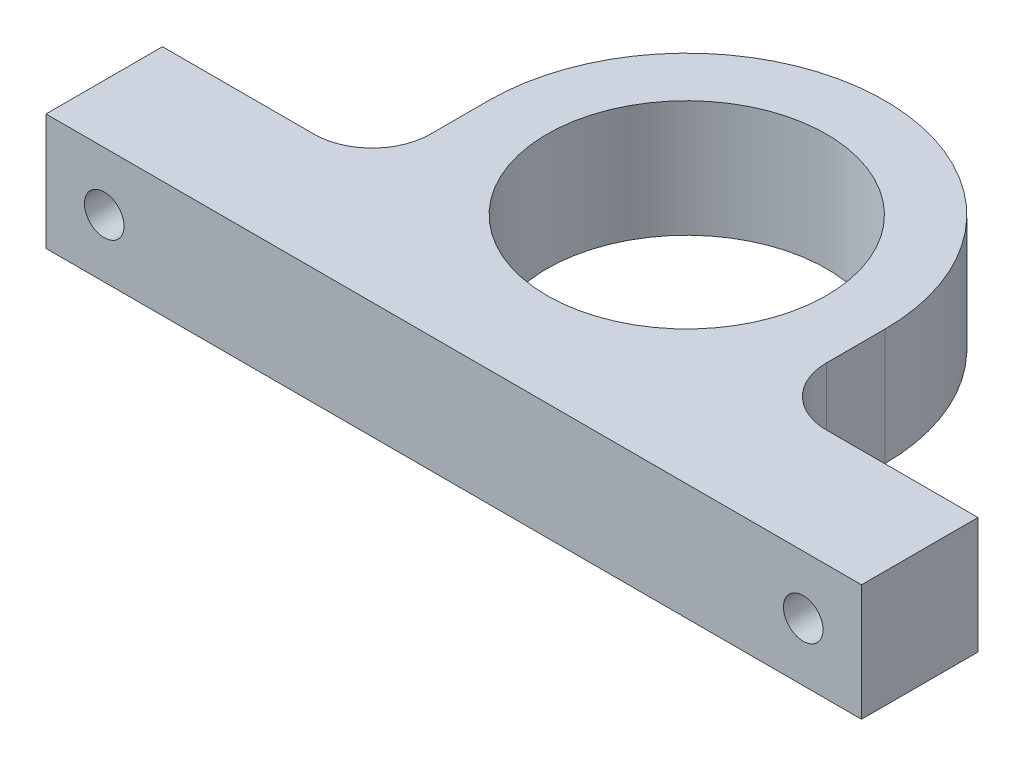
SolidWorks part; units mm, degrees
ref_plane "Front Plane" through (0, 0, 0) normal (0, 0, 1) x (1, 0, 0)
ref_plane "Top Plane" through (0, 0, 0) normal (0, 1, 0) x (1, 0, 0)
ref_plane "Right Plane" through (0, 0, 0) normal (1, 0, 0) x (0, 0, -1)
sketch "Sketch1" plane through (0, 0, 0) normal (0, 1, 0) x (1, 0, 0)
  line L0 (0, 0) -> (0, 20) construction
  line L5 (35, 0) -> (-35, 0)
  line L6 (-35, 0) -> (-35, 10)
  line L7 (-17, 10) -> (-35, 10)
  line L8 (-17, 20) -> (-17, 10)
  line L9 (0, 20) -> (0, 120.2965) construction
  line L10 (17, 20) -> (17, 10)
  line L11 (17, 10) -> (35, 10)
  line L12 (35, 0) -> (35, 10)
  circle A0 centre (0, 20) radius 12
  arc A1 (17, 20) -> (-17, 20) centre (0, 20) ccw
  dimension "D1" = 24
  dimension "D2" = 35
  dimension "D4" = 5
  dimension "D3" = 10
  dimension "D5" = 20
extrude "Boss-Extrude1" add sketch "Sketch1" along normal blind 10
fillet "Fillet1" radius 5 2 edges at (-17, 5, -10) (17, 5, -10)
sketch "Sketch2" plane through (0, 0, -10) normal (0, 0, -1) x (-1, 0, 0)
  line L0 (0, 0) -> (0, 10) construction
  line L1 (-17, 0) -> (17, 0) construction
  line L2 (17, 10) -> (-17, 10) construction
  line L3 (-35, 10) -> (-22, 10) construction
  line L4 (-35, 10) -> (-35, 0) construction
  point P0 (-30, 5)
  point P7 (0, 0)
  point P8 (30, 5)
  dimension "D1" = 5
  dimension "D2" = 5
hole_wizard "CSK for M3 Flat Head Machine Screw1" positions "3DSketch1" profile "Sketch3" countersink size "M3" standard "ANSI Metric" end condition through all
sketch3d "3DSketch1"
  point P0 (30, 5, -10)
  point P3 (-30, 5, -10)
sketch "Sketch3" plane through (30, 5, -10) normal (1, 0, 0) x (0, 1, 0)
  line L0 (0, 0) -> (0, 10)
  line L1 (0, 10) -> (1.7, 10)
  line L2 (1.7, 10) -> (1.7, 1.45)
  line L3 (1.7, 1.45) -> (3.15, 0)
  line L5 (3.15, 0) -> (0, 0)
  line L6 (-1.7, 1.45) -> (-3.15, 0) construction
  line L11 (0, -6.35) -> (0, 107.95) construction
  dimension "Thru Hole Dia." = 3.4
  dimension "Thru Hole Depth" = 10
  dimension "Near C'Sink Dia." = 6.3
  dimension "Near C'Sink Angle" = 90
